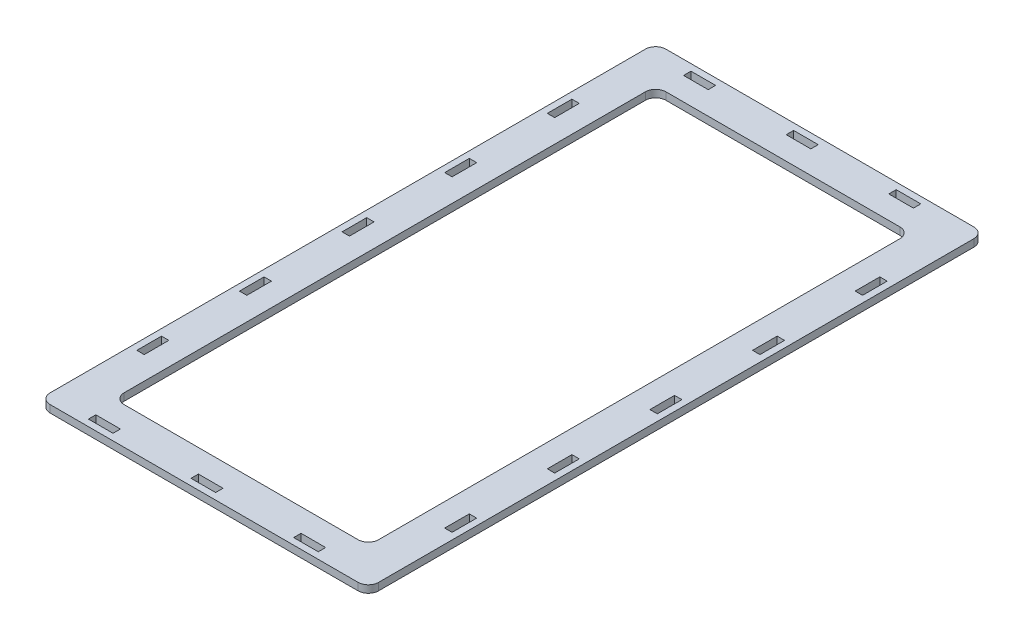
SolidWorks part; units mm, degrees
ref_plane "前视基准面" through (0, 0, 0) normal (0, 0, 1) x (1, 0, 0)
ref_plane "上视基准面" through (0, 0, 0) normal (0, 1, 0) x (1, 0, 0)
ref_plane "右视基准面" through (0, 0, 0) normal (1, 0, 0) x (0, 0, -1)
other "Configuration Table"
sketch "草图1" plane through (0, 0, 0) normal (0, 1, 0) x (1, 0, 0)
  line L1 (-400, 750) -> (400, 750)
  line L2 (-400, 750) -> (-400, -750)
  line L3 (-400, -750) -> (400, -750)
  line L4 (400, 750) -> (400, -750)
  line L5 (-384, -470) -> (-366, -470)
  line L6 (-384, -470) -> (-384, -530)
  line L7 (-384, -530) -> (-366, -530)
  line L8 (-366, -470) -> (-366, -530)
  line L9 (-298, -734) -> (-238, -734)
  line L10 (-298, -734) -> (-298, -716)
  line L11 (-298, -716) -> (-238, -716)
  line L12 (-238, -734) -> (-238, -716)
  line L13 (-310, 660) -> (310, 660)
  line L14 (-310, 660) -> (-310, -660)
  line L15 (-310, -660) -> (310, -660)
  line L16 (310, 660) -> (310, -660)
  point P4 (-400, 0)
  point P6 (0, -750)
  point P11 (-384, -500)
  point P20 (0, -660)
  point P21 (-310, 0)
  point P23 (-238, -725)
  point P24 (-375, -530)
  dimension "D1" = 800
  dimension "D2" = 1500
  dimension "D3" = 250
  dimension "D4" = 18
  dimension "D5" = 60
  dimension "D6" = 90
  dimension "D7" = 90
  dimension "D8" = 60
  dimension "D9" = 18
  dimension "D10" = 102
  dimension "D11" = 25
  dimension "D12" = 25
  dimension "D13" = 16
extrude "凸台-拉伸1" add sketch "草图1" along normal blind 18 contours L2 L3 L4 L1 | L14 L15 L16 L13
extrude "切除-拉伸1" cut sketch "草图1<5>" along normal through all contours L7 L8 L5 L6
sketch "草图1<5>" plane through (0, 0, 0) normal (0, 1, 0) x (1, 0, 0) same geometry as "草图1"
pattern_linear "阵列(线性)1" count 5 spacing 250 along (0, 0, -1) of "切除-拉伸1"
mirror "镜向1" about plane through (0, 0, 0) normal (1, 0, 0) of "切除-拉伸1", "阵列(线性)1"
extrude "切除-拉伸2" cut sketch "草图1<4>" along normal through all contours L12 L11 L10 L9
sketch "草图1<4>" plane through (0, 0, 0) normal (0, 1, 0) x (1, 0, 0) same geometry as "草图1"
pattern_linear "阵列(线性)2" count 3 spacing 250 along (1, 0, 0) of "切除-拉伸2"
mirror "镜向2" about plane through (0, 0, 0) normal (0, 0, 1) of "阵列(线性)2", "切除-拉伸2"
fillet "圆角1" radius 25 4 edges at (-400, 9, -750) (400, 9, -750) (400, 9, 750) (-400, 9, 750)
fillet "圆角2" radius 25 4 edges at (-310, 9, -660) (310, 9, -660) (310, 9, 660) (-310, 9, 660)
